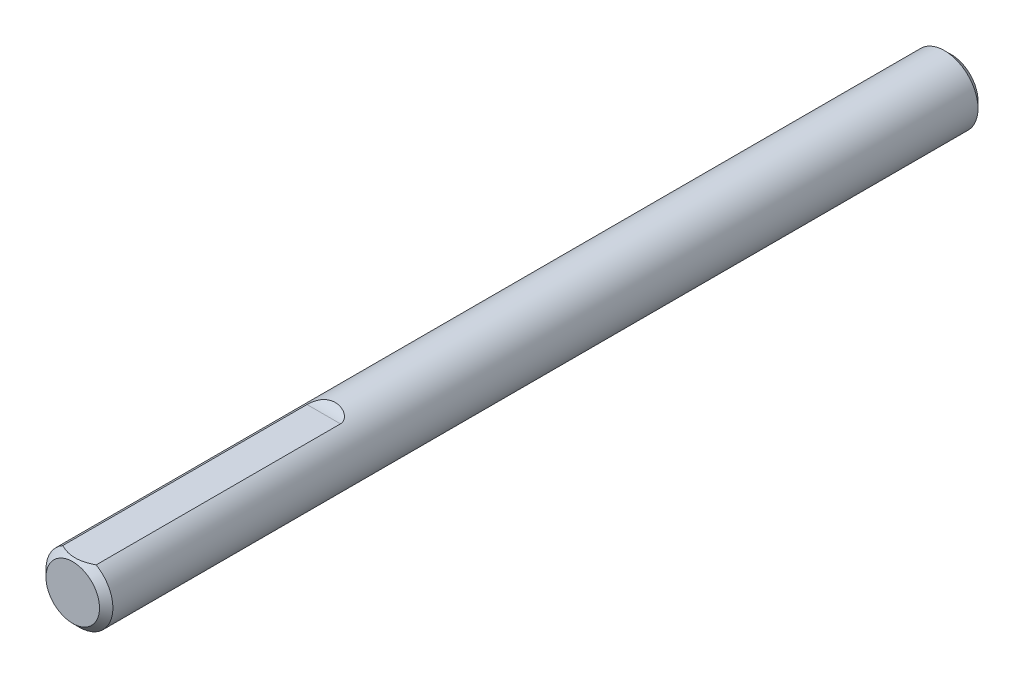
SolidWorks part; units mm, degrees
ref_plane "Front" through (0, 0, 0) normal (0, 0, 1) x (1, 0, 0)
ref_plane "Top" through (0, 0, 0) normal (0, 1, 0) x (1, 0, 0)
ref_plane "Right" through (0, 0, 0) normal (1, 0, 0) x (0, 0, -1)
sketch "Sketch1" plane through (0, 0, 0) normal (0, 0, 1) x (1, 0, 0)
  circle A0 centre (0, 0) radius 3.175
  dimension "D1" = 6.35
extrude "Extrude1" add sketch "Sketch1" along normal mid plane 83.3438
chamfer "Chamfer1" distance 0.635 angle 45 2 edges at (3.175, 0, -41.6719) (3.175, 0, 41.6719)
ref_plane "Plane1" through (0, 0, 16.2719) normal (0, 0, 1) x (1, 0, 0)
sketch "Sketch13" plane through (0, 0, 16.2719) normal (0, 0, 1) x (1, 0, 0)
  line L3 (-1.5875, 2.7496) -> (1.5875, 2.7496)
  circle A0 centre (0, 0) radius 3.175 construction
  arc A1 (1.5875, 2.7496) -> (-1.5875, 2.7496) centre (0, 0) ccw
  dimension "D1" = 3.175
extrude "Extrude7" cut sketch "Sketch13" along normal through all
fillet "Fillet1" radius 1.5875 1 edges at (0, 2.7496, 16.2719)
equation "\"D1@Chamfer1\" = \"D1@Sketch1\" * .1"
equation "\"D1@Sketch13\" = \"D1@Sketch1\" * .5"
